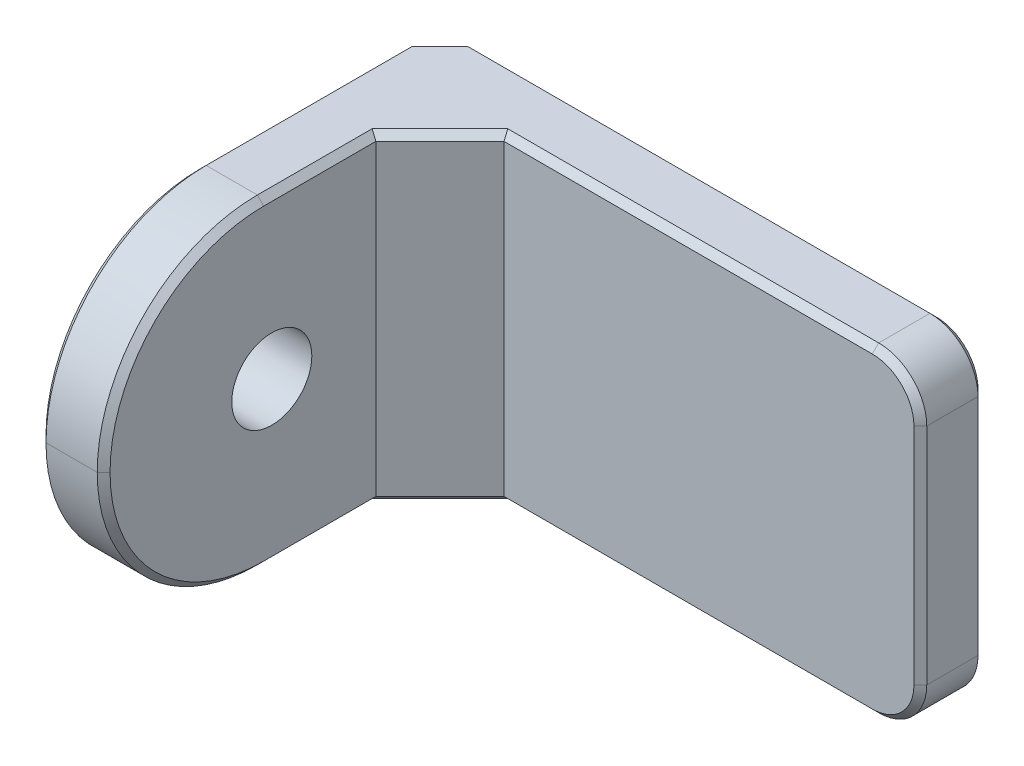
SolidWorks part; units mm, degrees
ref_plane "前视基准面" through (0, 0, 0) normal (0, 0, 1) x (1, 0, 0)
ref_plane "上视基准面" through (0, 0, 0) normal (0, 1, 0) x (1, 0, 0)
ref_plane "右视基准面" through (0, 0, 0) normal (1, 0, 0) x (0, 0, -1)
other "Configuration Table"
sketch "草图1" plane through (0, 0, 0) normal (0, 1, 0) x (1, 0, 0)
  line L1 (0, 0) -> (4, 0)
  line L2 (0, 0) -> (0, 25)
  line L3 (0, 25) -> (4, 25)
  line L4 (4, 0) -> (4, 21)
  line L5 (4, 25) -> (34, 25)
  line L7 (4, 21) -> (34, 21)
  line L8 (34, 25) -> (34, 21)
  dimension "D1" = 25
  dimension "D2" = 4
  dimension "D3" = 30
  dimension "D4" = 4
extrude "凸台-拉伸1" add sketch "草图1" along normal blind 20
sketch "草图2" plane through (4, 0, 0) normal (1, 0, 0) x (0, 0, -1)
  line L0 (0, 20) -> (0, 0) construction
  line L1 (0, 20) -> (21, 20) construction
  circle A0 centre (10.5, 10) radius 2.5
  point P4 (0, 10)
  point P7 (10.5, 20)
  dimension "D1" = 5
  dimension "D2" = 0
  dimension "D3" = 0
extrude "切除-拉伸1" cut sketch "草图2" against normal blind 20
fillet "圆角1" radius 10 2 edges at (2, 0, 0) (2, 20, 0)
chamfer "倒角1" distance 4 angle 45 1 edges at (4, 10, -21)
chamfer "倒角2" distance 2 angle 45 1 edges at (0, 10, -25)
fillet "圆角2" radius 3 2 edges at (34, 0, -23) (34, 20, -23)
chamfer "倒角3" distance 0.4 angle 45 22 edges at (1, 0, -24) (16.5, 0, -25) (33.1213, 0.8787, -25) (34, 10, -25) (33.1213, 19.1213, -25) (16.5, 20, -25) (1, 20, -24) (0, 0, -16.5) (0, 2.9289, -2.9289) (0, 20, -16.5) (0, 17.0711, -2.9289) (6, 0, -19) (19.5, 0, -21) (33.1213, 0.8787, -21) (4, 0, -13.5) (34, 10, -21) (4, 2.9289, -2.9289) (33.1213, 19.1213, -21) (4, 17.0711, -2.9289) (19.5, 20, -21) (6, 20, -19) (4, 20, -13.5)
